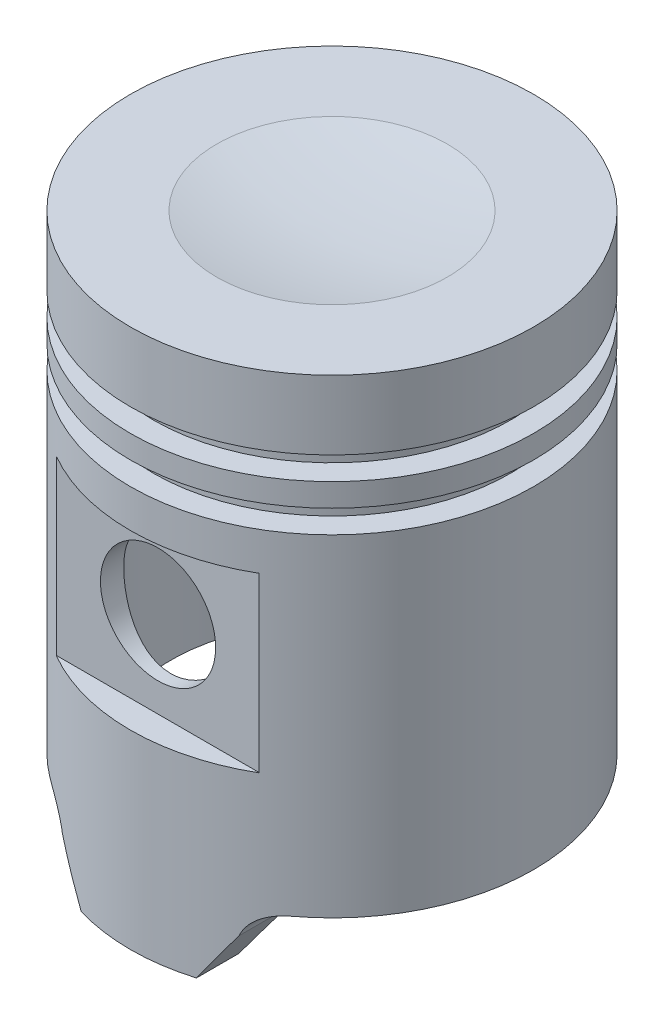
SolidWorks part; units mm, degrees
ref_plane "Front Plane" through (0, 0, 0) normal (0, 0, 1) x (1, 0, 0)
ref_plane "Top Plane" through (0, 0, 0) normal (0, 1, 0) x (1, 0, 0)
ref_plane "Right Plane" through (0, 0, 0) normal (1, 0, 0) x (0, 0, -1)
sketch "Sketch2" plane through (0, 0, 0) normal (1, 0, 0) x (0, 0, -1)
  line L4 (0, 74.5117) -> (0, -77.8883) construction
  line L11 (0, -6.35) -> (17.78, -6.35)
  line L13 (22.225, -58.166) -> (17.78, -58.166)
  line L14 (17.78, -6.35) -> (17.78, -58.166)
  line L16 (19.685, -6.35) -> (19.685, -8.89)
  line L17 (22.225, 1.27) -> (22.225, -6.35)
  line L18 (22.225, -6.35) -> (19.685, -6.35)
  line L19 (19.685, -8.89) -> (22.225, -8.89)
  line L20 (22.225, -8.89) -> (22.225, -11.43)
  line L21 (22.225, -11.43) -> (19.685, -11.43)
  line L22 (19.685, -11.43) -> (19.685, -13.97)
  line L23 (19.685, -13.97) -> (22.225, -13.97)
  line L24 (22.225, -13.97) -> (22.225, -19.431)
  line L29 (22.225, -38.481) -> (22.225, -58.166)
  line L30 (12.7127, 1.27) -> (22.225, 1.27)
  line L31 (0, 0) -> (0, -6.35)
  line L32 (22.225, -19.431) -> (22.225, -38.481)
  arc A1 (0, 0) -> (12.7127, 1.27) centre (0, 64.262) ccw
  dimension "D8" = 64.262
  dimension "D9" = 58.166
  dimension "D3" = 19.05
  dimension "D1" = 12.7127
  dimension "D2" = 17.78
  dimension "D4" = 19.685
  dimension "D5" = 22.225
  dimension "D6" = 6.35
  dimension "D7" = 38.481
revolve "Revolve1" add sketch "Sketch2" angle 360 about L4
ref_plane "Plane1" through (0, 0, 22.225) normal (0, 0, 1) x (1, 0, 0)
sketch "Sketch4" plane through (0, 0, 22.225) normal (0, 0, 1) x (1, 0, 0)
  line L0 (0, 1.27) -> (0, -56.642) construction
  line L1 (12.7127, 1.27) -> (-12.7127, 1.27) construction
  line L2 (-22.225, -58.166) -> (22.225, -58.166) construction
  line L3 (-11.176, -37.211) -> (11.176, -37.211)
  line L4 (-11.176, -37.211) -> (-11.176, -18.161)
  line L5 (-11.176, -18.161) -> (11.176, -18.161)
  line L6 (11.176, -37.211) -> (11.176, -18.161)
  line L7 (-11.176, -37.211) -> (11.176, -18.161) construction
  line L8 (-11.176, -18.161) -> (11.176, -37.211) construction
  point P5 (0, -27.686)
  point P10 (0, 0)
  point P11 (0, 0)
  dimension "D1" = 30.48
  dimension "D2" = 19.05
  dimension "D3" = 22.352
extrude "Cut-Extrude5" cut sketch "Sketch4" against normal blind 3.048
sketch "Sketch5" plane through (0, 0, 19.177) normal (0, 0, 1) x (1, 0, 0)
  line L2 (-22.225, -58.166) -> (22.225, -58.166) construction
  line L3 (11.176, -37.211) -> (11.176, -18.161) construction
  circle A0 centre (0, -27.686) radius 6.35
  point P2 (0, 0)
  dimension "D1" = 30.48
  dimension "D2" = 12.7
  dimension "D3" = 11.176
extrude "Cut-Extrude6" cut sketch "Sketch5" against normal up to surface (2.5696 mm away) contours A0 up to face at (0, -58.166, 17.78)
ref_plane "Plane2" through (0, 0, -22.225) normal (0, 0, -1) x (-1, 0, 0)
sketch "Sketch7" plane through (0, 0, -22.225) normal (0, 0, -1) x (-1, 0, 0)
  line L0 (0, 1.27) -> (0, -64.5597) construction
  line L1 (22.225, 1.27) -> (-22.225, 1.27) construction
  line L2 (-22.225, -58.166) -> (22.225, -58.166) construction
  line L3 (-11.176, -37.211) -> (11.176, -37.211)
  line L4 (-11.176, -37.211) -> (-11.176, -18.161)
  line L5 (-11.176, -18.161) -> (11.176, -18.161)
  line L6 (11.176, -37.211) -> (11.176, -18.161)
  line L7 (-11.176, -37.211) -> (11.176, -18.161) construction
  line L8 (-11.176, -18.161) -> (11.176, -37.211) construction
  point P5 (0, -27.686)
  point P10 (0, 0)
  dimension "D1" = 19.05
  dimension "D2" = 22.352
  dimension "D3" = 30.48
extrude "Cut-Extrude7" cut sketch "Sketch7" against normal blind 3.048 contours L4 L3 L6 L5
sketch "Sketch8" plane through (0, 0, -19.177) normal (0, 0, -1) x (-1, 0, 0)
  line L0 (-22.225, -58.166) -> (22.225, -58.166) construction
  line L1 (11.176, -37.211) -> (11.176, -18.161) construction
  circle A0 centre (0, -27.686) radius 6.35
  dimension "D1" = 30.48
  dimension "D2" = 12.7
  dimension "D3" = 11.176
extrude "Cut-Extrude8" cut sketch "Sketch8" against normal blind 3.048 contours A0
sketch "Sketch10" plane through (0, 0, 22.225) normal (0, 0, 1) x (1, 0, 0)
  line L0 (0, 0) -> (0, -64.5597) construction
  line L1 (-6.35, -58.166) -> (6.35, -58.166)
  line L2 (-22.225, -58.166) -> (22.225, -58.166) construction
  line L3 (-9.7391, -53.0842) -> (-6.35, -58.166)
  line L4 (-13.335, -50.5419) -> (-22.225, -50.5419)
  line L5 (13.335, -50.5419) -> (22.225, -50.5419)
  line L6 (22.225, -58.166) -> (22.225, -13.97) construction
  line L7 (9.7391, -53.0842) -> (6.35, -58.166)
  line L8 (-22.225, -50.5419) -> (-22.225, -58.166)
  line L9 (-22.225, -58.166) -> (22.225, -58.166)
  line L10 (22.225, -58.166) -> (22.225, -50.5419)
  arc A0 (13.335, -50.5419) -> (9.7391, -53.0842) centre (13.335, -54.356) ccw
  arc A1 (-13.335, -50.5419) -> (-9.7391, -53.0842) centre (-13.335, -54.356) cw
  point P11 (0, -58.166)
  dimension "D1" = 3.8141
  dimension "D2" = 3.81
  dimension "D3" = 8.89
  dimension "D4" = 6.35
  dimension "D5" = 9.7391
extrude "Cut-Extrude9" cut sketch "Sketch10" against normal through all and the other way through all contours A1 L4 L8 L9 L3 | L5 A0 L7 L9 L10 region at (15.4878, -54.6104, 22.225) region at (-15.4878, -54.6104, 22.225)
